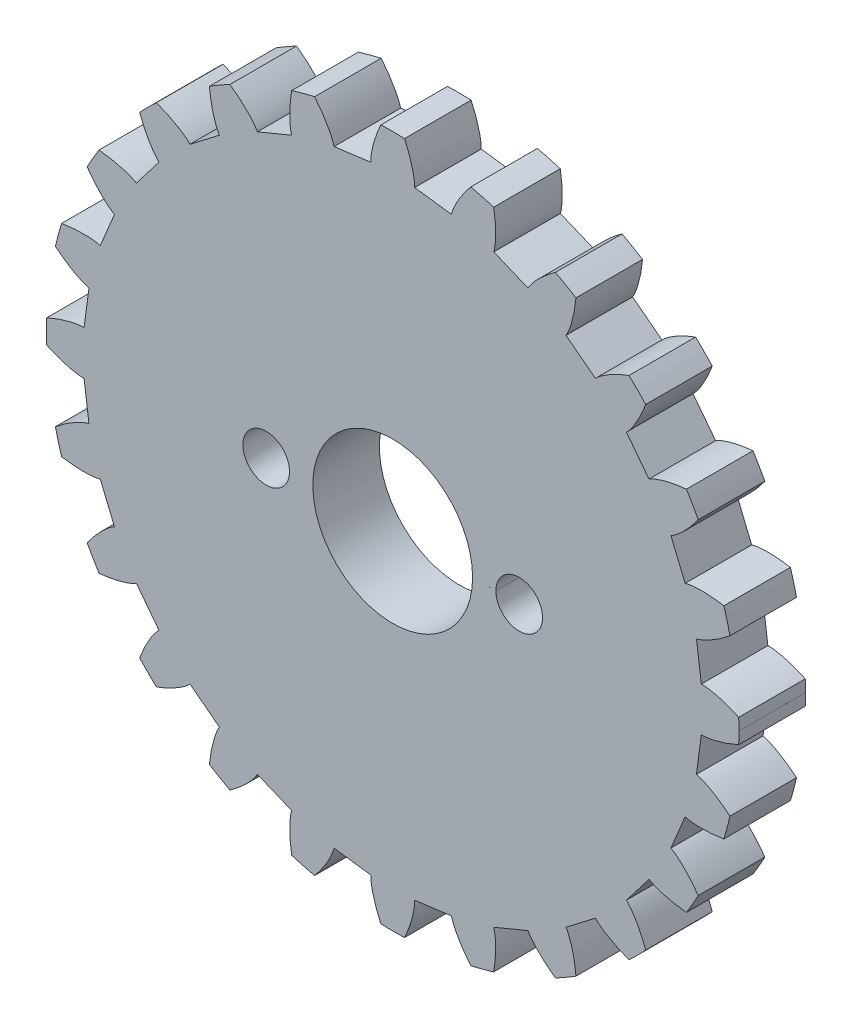
SolidWorks part; units mm, degrees
material "Plain Carbon Steel"
ref_plane "Front Plane" through (0, 0, 0) normal (0, 0, 1) x (1, 0, 0)
ref_plane "Top Plane" through (0, 0, 0) normal (0, 1, 0) x (1, 0, 0)
ref_plane "Right Plane" through (0, 0, 0) normal (1, 0, 0) x (0, 0, -1)
sketch "Sketch1" plane through (0, 0, 0) normal (0, 1, 0) x (1, 0, 0)
  line L0 (0, 0) -> (26, 0)
  line L1 (26, 0) -> (26, -5)
  line L2 (26, -5) -> (0, -5)
  line L3 (0, -5) -> (0, 0)
  line L4 (0, -1) -> (0, -4) construction
  dimension "D1" = 26
  dimension "D2" = 5
revolve "Revolve1" add sketch "Sketch1" angle 360 about L4
sketch "Sketch2" plane through (0, 0, 0) normal (0, 0, 1) x (1, 0, 0)
  spline S0 degree 4 poles (23.177, 1.6482) (23.1813, 1.6485) (23.1935, 1.6491) (23.2164, 1.6496) (23.254, 1.6497) (23.3019, 1.6487) (23.3639, 1.646) (23.437, 1.6411) (23.5174, 1.6339) (23.6049, 1.6241) (23.6923, 1.6126) (23.7796, 1.5995) (23.8665, 1.585) (23.9718, 1.5657) (24.0981, 1.5401) (24.2458, 1.5067) (24.4133, 1.4648) (24.5839, 1.4176) (24.7518, 1.3675) (24.9214, 1.3128) (25.0854, 1.2568) (25.2557, 1.1944) (25.4128, 1.1347) (25.5887, 1.063) (25.7306, 1.0037) (25.9177, 0.9206) (26.028, 0.8699) (26.1572, 0.8089) (26.2145, 0.7809) (26.2497, 0.7637) knots 0 0 0 0 0 0.005377 0.015084 0.028532 0.04661 0.064855 0.092111 0.119476 0.146842 0.174209 0.201575 0.228941 0.256307 0.307035 0.361767 0.4165 0.471232 0.525964 0.580697 0.635429 0.690161 0.744894 0.799626 0.854358 0.909091 0.954545 1 1 1 1 1 construction
  spline S1 degree 4 poles (23.177, 1.6482) (23.1813, 1.6485) (23.1935, 1.6491) (23.2164, 1.6496) (23.254, 1.6497) (23.3019, 1.6487) (23.3639, 1.646) (23.437, 1.6411) (23.5174, 1.6339) (23.6049, 1.6241) (23.6923, 1.6126) (23.7796, 1.5995) (23.8665, 1.585) (23.9718, 1.5657) (24.0981, 1.5401) (24.2458, 1.5067) (24.4133, 1.4648) (24.5839, 1.4176) (24.7518, 1.3675) (24.9214, 1.3128) (25.0854, 1.2568) (25.2557, 1.1944) (25.4128, 1.1347) (25.5887, 1.063) (25.7306, 1.0037) (25.8771, 0.9386) (25.9484, 0.9063) (25.9848, 0.8896) knots 0 0 0 0 0 0.005377 0.015084 0.028532 0.04661 0.064855 0.092111 0.119476 0.146842 0.174209 0.201575 0.228941 0.256307 0.307035 0.361767 0.4165 0.471232 0.525964 0.580697 0.635429 0.690161 0.744894 0.799626 0.854358 0.909091 0.909091 0.909091 0.909091 0.909091
  spline S2 degree 4 poles (22.8139, 4.4066) (22.8181, 4.4075) (22.83, 4.41) (22.8523, 4.4154) (22.8886, 4.4251) (22.9346, 4.4385) (22.9938, 4.4571) (23.0631, 4.4807) (23.1389, 4.5085) (23.221, 4.5406) (23.3024, 4.5744) (23.3833, 4.6096) (23.4635, 4.6461) (23.5602, 4.692) (23.6756, 4.7494) (23.8096, 4.8199) (23.9605, 4.9038) (24.1131, 4.9935) (24.2624, 5.0853) (24.412, 5.1821) (24.556, 5.2786) (24.7043, 5.3829) (24.8406, 5.4813) (24.9919, 5.5961) (25.1137, 5.69) (25.2728, 5.8188) (25.3663, 5.8963) (25.4752, 5.9886) (25.5233, 6.0305) (25.553, 6.0563) knots 0 0 0 0 0 0.005377 0.015084 0.028532 0.04661 0.064855 0.092111 0.119476 0.146842 0.174209 0.201575 0.228941 0.256307 0.307035 0.361767 0.4165 0.471232 0.525964 0.580697 0.635429 0.690161 0.744894 0.799626 0.854358 0.909091 0.954545 1 1 1 1 1 construction
  spline S3 degree 4 poles (22.8139, 4.4066) (22.8181, 4.4075) (22.83, 4.41) (22.8523, 4.4154) (22.8886, 4.4251) (22.9346, 4.4385) (22.9938, 4.4571) (23.0631, 4.4807) (23.1389, 4.5085) (23.221, 4.5406) (23.3024, 4.5744) (23.3833, 4.6096) (23.4635, 4.6461) (23.5602, 4.692) (23.6756, 4.7494) (23.8096, 4.8199) (23.9605, 4.9038) (24.1131, 4.9935) (24.2624, 5.0853) (24.412, 5.1821) (24.556, 5.2786) (24.7043, 5.3829) (24.8406, 5.4813) (24.9919, 5.5961) (25.1137, 5.69) (25.2383, 5.7909) (25.2988, 5.8405) (25.3296, 5.8661) knots 0 0 0 0 0 0.005377 0.015084 0.028532 0.04661 0.064855 0.092111 0.119476 0.146842 0.174209 0.201575 0.228941 0.256307 0.307035 0.361767 0.4165 0.471232 0.525964 0.580697 0.635429 0.690161 0.744894 0.799626 0.854358 0.909091 0.909091 0.909091 0.909091 0.909091
  spline S4 degree 4 poles (22.7775, 4.6829) (22.7807, 4.6587) (22.7869, 4.6115) (22.7943, 4.5548) (22.8117, 4.4234) (22.8198, 4.3613) (22.8431, 4.1843) (22.8567, 4.0812) (22.8772, 3.9253) (22.894, 3.798) (22.9128, 3.6552) (22.9298, 3.5256) (22.9476, 3.3909) (22.9638, 3.2678) (22.9809, 3.1377) (22.9981, 3.0069) (23.0161, 2.8701) (23.0345, 2.7307) (23.0532, 2.5884) (23.0711, 2.4528) (23.0907, 2.3041) (23.1075, 2.1759) (23.1295, 2.009) (23.1444, 1.8957) (23.1712, 1.6924) (23.1801, 1.6248) (23.1989, 1.4819) (23.2062, 1.4268) (23.211, 1.39) (23.2135, 1.371) knots 0 0 0 0 0 0.028849 0.052878 0.083333 0.124324 0.163161 0.206806 0.246995 0.288912 0.331781 0.370109 0.409255 0.448242 0.482806 0.525716 0.568843 0.611704 0.653696 0.694186 0.738248 0.782176 0.823818 0.871169 0.916667 0.958584 0.979292 1 1 1 1 1 construction
  spline S5 degree 4 poles (22.8139, 4.4066) (22.8176, 4.3783) (22.8244, 4.3263) (22.8431, 4.1843) (22.8567, 4.0812) (22.8772, 3.9253) (22.894, 3.798) (22.9128, 3.6552) (22.9298, 3.5256) (22.9476, 3.3909) (22.9638, 3.2678) (22.9809, 3.1377) (22.9981, 3.0069) (23.0161, 2.8701) (23.0345, 2.7307) (23.0532, 2.5884) (23.0711, 2.4528) (23.0907, 2.3041) (23.1075, 2.1759) (23.1295, 2.009) (23.1444, 1.8957) (23.1648, 1.7407) (23.1729, 1.6796) (23.177, 1.6482) knots 0.083333 0.083333 0.083333 0.083333 0.083333 0.124324 0.163161 0.206806 0.246995 0.288912 0.331781 0.370109 0.409255 0.448242 0.482806 0.525716 0.568843 0.611704 0.653696 0.694186 0.738248 0.782176 0.823818 0.871169 0.916667 0.916667 0.916667 0.916667 0.916667
  spline S6 degree 4 poles (22.5838, 0.7731) (23.0672, 0.7897) (23.6703, 0.8103) (25.5078, 0.8732) (26.4501, 0.9055) (28.7534, 0.9843) (30.1565, 1.0324) (32.1757, 1.1015) (33.8803, 1.1599) (35.8485, 1.2272) (37.6947, 1.2904) (39.6506, 1.3574) (41.5311, 1.4218) (43.4321, 1.4869) (45.2708, 1.5498) (47.0129, 1.6094) (48.7163, 1.6678) (50.2285, 1.7195) (51.6384, 1.7678) (52.9613, 1.8131) (54.2605, 1.8576) (55.4506, 1.8983) (56.8677, 1.9468) (57.8956, 1.982) (59.7111, 2.0441) (60.37, 2.0667) (62.0621, 2.1246) (62.6297, 2.1441) (63.1349, 2.1614) (63.3918, 2.1702) knots 0 0 0 0 0 0.041667 0.083333 0.123541 0.166753 0.209392 0.256181 0.300395 0.346612 0.394832 0.44205 0.489269 0.53291 0.580271 0.622911 0.660113 0.699653 0.729462 0.759701 0.79242 0.822588 0.854043 0.885331 0.916667 0.957078 0.978539 1 1 1 1 1 construction
  spline S7 degree 4 poles (25.9848, 0.8896) (26.3263, 0.9013) (27.0223, 0.9251) (28.7534, 0.9843) (30.1565, 1.0324) (32.1757, 1.1015) (33.8803, 1.1599) (35.8485, 1.2272) (37.6947, 1.2904) (39.6506, 1.3574) (41.5311, 1.4218) (43.4321, 1.4869) (45.2708, 1.5498) (47.0129, 1.6094) (48.7163, 1.6678) (50.2285, 1.7195) (51.6384, 1.7678) (52.9613, 1.8131) (54.2605, 1.8576) (55.4506, 1.8983) (56.8677, 1.9468) (57.8956, 1.982) (59.1656, 2.0255) (59.6986, 2.0437) (59.9648, 2.0528) knots 0.083333 0.083333 0.083333 0.083333 0.083333 0.123541 0.166753 0.209392 0.256181 0.300395 0.346612 0.394832 0.44205 0.489269 0.53291 0.580271 0.622911 0.660113 0.699653 0.729462 0.759701 0.79242 0.822588 0.854043 0.885331 0.916667 0.916667 0.916667 0.916667 0.916667
  spline S8 degree 4 poles (59.9935, 0.8853) (59.9921, 0.9686) (59.9891, 1.1296) (59.9859, 1.3474) (59.9691, 1.9373) (59.9603, 2.1956) (59.9292, 2.9561) (59.9042, 3.3875) (59.8676, 4.0111) (59.8299, 4.5186) (59.7847, 5.0956) (59.7358, 5.63) (59.6811, 6.1892) (59.6218, 6.733) (59.5573, 7.2845) (59.4875, 7.8317) (59.4133, 8.3783) (59.3328, 8.9276) (59.2494, 9.4683) (59.1575, 10.0226) (59.0664, 10.5515) (58.9607, 11.1205) (58.8658, 11.6204) (58.7398, 12.2323) (58.6522, 12.6554) (58.4855, 13.3981) (58.4271, 13.6498) (58.2906, 14.224) (58.2374, 14.4352) (58.1986, 14.5915) (58.1784, 14.6723) knots 0 0 0 0 0 0.020959 0.041918 0.083333 0.123016 0.162698 0.202381 0.242063 0.281746 0.321429 0.361111 0.400794 0.440476 0.480159 0.519841 0.559524 0.599206 0.638889 0.678571 0.718254 0.757937 0.797619 0.837302 0.876984 0.916667 0.958082 0.979041 1 1 1 1 1 construction
  spline S9 degree 4 poles (59.9648, 2.0528) (59.9608, 2.1679) (59.9523, 2.3919) (59.9292, 2.9561) (59.9042, 3.3875) (59.8676, 4.0111) (59.8299, 4.5186) (59.7847, 5.0956) (59.7358, 5.63) (59.6811, 6.1892) (59.6218, 6.733) (59.5573, 7.2845) (59.4875, 7.8317) (59.4133, 8.3783) (59.3328, 8.9276) (59.2494, 9.4683) (59.1575, 10.0226) (59.0664, 10.5515) (58.9607, 11.1205) (58.8658, 11.6204) (58.7398, 12.2323) (58.6522, 12.6554) (58.5285, 13.2064) (58.4788, 13.425) (58.4528, 13.5371) knots 0.083333 0.083333 0.083333 0.083333 0.083333 0.123016 0.162698 0.202381 0.242063 0.281746 0.321429 0.361111 0.400794 0.440476 0.480159 0.519841 0.559524 0.599206 0.638889 0.678571 0.718254 0.757937 0.797619 0.837302 0.876984 0.916667 0.916667 0.916667 0.916667 0.916667
  spline S10 degree 4 poles (61.7739, 14.3063) (61.7039, 14.2901) (61.5796, 14.2613) (61.4666, 14.2351) (60.8505, 14.0924) (60.4206, 13.9929) (58.8446, 13.6279) (58.2932, 13.5002) (56.7254, 13.1371) (55.8234, 12.9282) (54.568, 12.6374) (53.4429, 12.3769) (52.0511, 12.0546) (50.5992, 11.7183) (49.0504, 11.3596) (47.4563, 10.9905) (45.8632, 10.6215) (44.3102, 10.2618) (42.7618, 9.9032) (41.1907, 9.5394) (39.6063, 9.1725) (38.0428, 8.8104) (36.385, 8.4264) (34.8232, 8.0647) (33.0593, 7.6562) (31.5267, 7.3013) (29.6304, 6.8621) (28.2966, 6.5532) (25.8856, 5.9949) (25.0823, 5.8088) (23.5273, 5.4487) (22.7343, 5.2651) (22.3407, 5.1739) (22.1153, 5.1217) (22.0166, 5.0988) knots 0 0 0 0 0 0.005334 0.010668 0.021335 0.042671 0.083333 0.112698 0.136843 0.163043 0.191355 0.228657 0.25743 0.298405 0.34029 0.382676 0.419052 0.457933 0.497208 0.537818 0.578079 0.616034 0.656645 0.70114 0.741113 0.784 0.826386 0.866769 0.916667 0.958333 0.979167 0.989583 1 1 1 1 1 construction
  spline S11 degree 4 poles (58.4528, 13.5371) (58.2096, 13.4808) (57.7636, 13.3775) (56.7254, 13.1371) (55.8234, 12.9282) (54.568, 12.6374) (53.4429, 12.3769) (52.0511, 12.0546) (50.5992, 11.7183) (49.0504, 11.3596) (47.4563, 10.9905) (45.8632, 10.6215) (44.3102, 10.2618) (42.7618, 9.9032) (41.1907, 9.5394) (39.6063, 9.1725) (38.0428, 8.8104) (36.385, 8.4264) (34.8232, 8.0647) (33.0593, 7.6562) (31.5267, 7.3013) (29.6304, 6.8621) (28.2966, 6.5532) (26.4619, 6.1283) (25.7428, 5.9618) (25.3296, 5.8661) knots 0.083333 0.083333 0.083333 0.083333 0.083333 0.112698 0.136843 0.163043 0.191355 0.228657 0.25743 0.298405 0.34029 0.382676 0.419052 0.457933 0.497208 0.537818 0.578079 0.616034 0.656645 0.70114 0.741113 0.784 0.826386 0.866769 0.916667 0.916667 0.916667 0.916667 0.916667
extrude "Cut-Extrude2" cut sketch "Sketch2" against normal blind 6 and the other way blind 6
ref_axis "Axis1" through (0, 0, -0.25) along (0, 0, 1)
pattern_circular "CirPattern2" count 24 over 360 about axis through (0, 0, 5) along (0, 0, -1) of "Cut-Extrude2"
sketch "Sketch3" plane through (0, 0, 0) normal (0, 0, 1) x (1, 0, 0)
  line L0 (0, 0) -> (26, -0.0001) construction
  circle A0 centre (0, 0) radius 6
  circle A1 centre (9.5, -0.0001) radius 1.75
  circle A2 centre (-9.5, 0) radius 1.75
  dimension "D1" = 12
  dimension "D2" = 3.5
  dimension "D3" = 3.5
extrude "Cut-Extrude4" cut sketch "Sketch3" against normal blind 7 and the other way blind 7
equation "\"TrigProbe\"= cos(60)"
equation "\"SqrProbe\"= sqr(2)"
equation "\"AtnProbe\"= atn(1)"
equation "\"ToothCount\" = 24"
equation "\"DP\"= 12.7"
equation "\"PA\"= 14.5"
equation "\"PArad\"= \"PA\" * 3.14159265358979 / 180"
equation "\"Rb\"= \"ToothCount\" / \"DP\" * cos(\"PA\") / 2"
equation "\"Ra\"= (\"ToothCount\" + 2) / \"DP\" / 2"
equation "\"Tmax\"= sqr(\"Ra\" * \"Ra\" / (\"Rb\" * \"Rb\") - 1)"
equation "\"Delta\"= 3.14159265358979 / (2 * \"ToothCount\") + tan(\"PA\") - \"PArad\""
equation "\"Gamma\"= 2 * 3.14159265358979 / \"ToothCount\""
equation "\"ThetaL\"= atn(\"Tmax\") * 3.14159265358979 / 180 - \"Tmax\" + \"Delta\""
equation "\"ThetaU\"= \"Tmax\" - atn(\"Tmax\") * 3.14159265358979 / 180 - \"Delta\" + \"Gamma\""
equation "\"D1@Sketch1\" = \"Ra\""
equation "\"D1@CirPattern2\" = \"ToothCount\""
